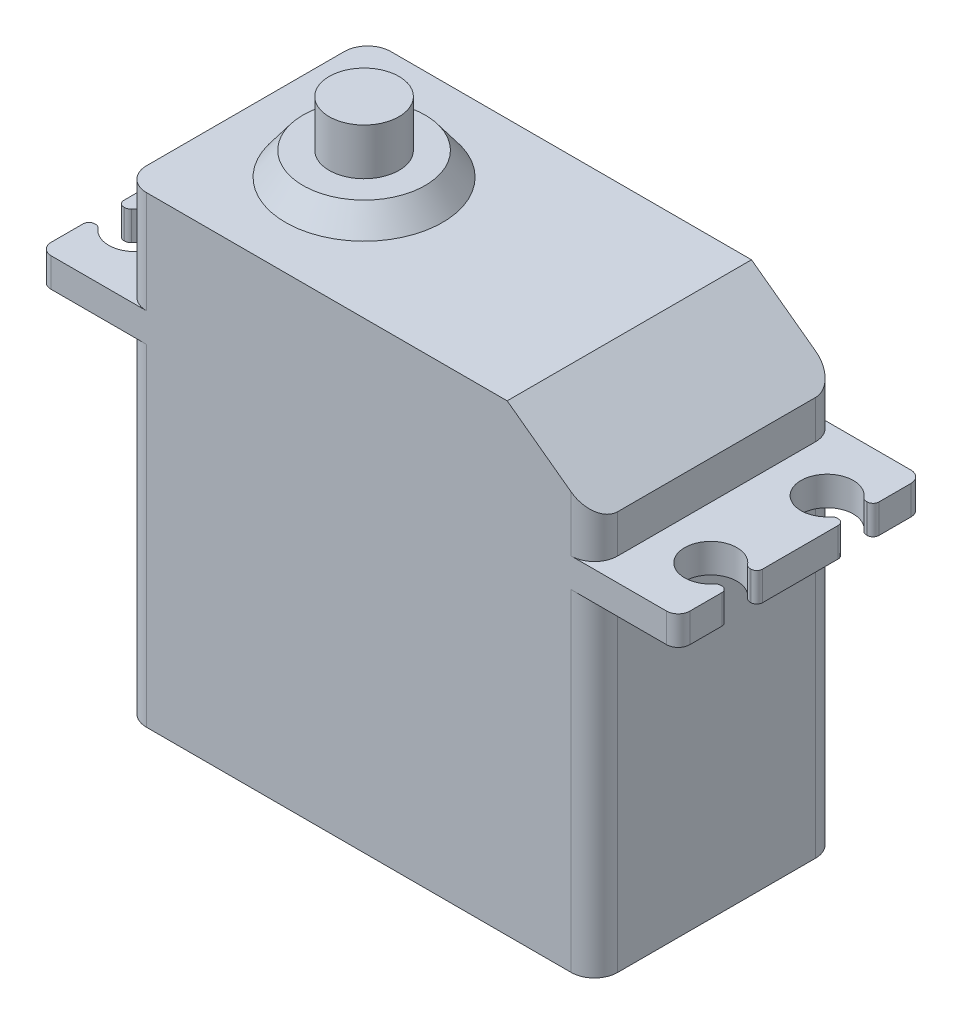
SolidWorks part; units mm, degrees
ref_plane "Plan de face" through (0, 0, 0) normal (0, 0, 1) x (1, 0, 0)
ref_plane "Plan de dessus" through (0, 0, 0) normal (0, 1, 0) x (1, 0, 0)
ref_plane "Plan de droite" through (0, 0, 0) normal (1, 0, 0) x (0, 0, -1)
sketch "Esquisse1" plane through (0, 0, 0) normal (0, 0, 1) x (1, 0, 0)
  line L0 (0, 0) -> (40.5, 0)
  line L1 (40.5, 0) -> (40.5, 34.3)
  line L2 (40.5, 34.3) -> (33, 39.8)
  line L3 (33, 39.8) -> (0, 39.8)
  line L4 (0, 39.8) -> (0, 0)
  dimension "D1" = 39.8
  dimension "D2" = 40.5
  dimension "D3" = 5.5
  dimension "D4" = 7.5
extrude "Extrusion1" add sketch "Esquisse1" against normal blind 21
sketch "Esquisse2" plane through (40.5, 0, 0) normal (1, 0, 0) x (0, 0, -1)
  line L0 (0, 28.5) -> (21, 28.5)
  line L1 (21, 0) -> (21, 34.3) construction
  line L2 (21, 28.5) -> (21, 31)
  line L3 (21, 31) -> (0, 31)
  line L4 (0, 31) -> (0, 28.5)
  line L5 (0, 0) -> (0, 34.3) construction
  line L6 (21, 0) -> (0, 0) construction
  dimension "D1" = 2.5
  dimension "D2" = 28.5
extrude "Extrusion2" add sketch "Esquisse2" along normal blind 7.2
sketch "Esquisse3" plane through (0, 0, 0) normal (-1, 0, 0) x (0, 0, 1)
  line L0 (-21, 31) -> (0, 31)
  line L1 (0, 31) -> (0, 28.5)
  line L2 (0, 28.5) -> (-21, 28.5)
  line L3 (-21, 39.8) -> (-21, 0) construction
  line L4 (0, 28.5) -> (-21, 28.5) construction
  line L5 (-21, 28.5) -> (-21, 31)
extrude "Extrusion3" add sketch "Esquisse3" along normal blind 7.2
sketch "Esquisse4" plane through (0, 31, 0) normal (0, 1, 0) x (-1, 0, 0)
  line L0 (-20.25, -21) -> (-20.25, 0) construction
  line L1 (-33, -21) -> (0, -21) construction
  line L2 (-33, 0) -> (0, 0) construction
  line L3 (7.2, -10.5) -> (-47.7, -10.5) construction
  line L4 (7.2, 0) -> (7.2, -21) construction
  line L5 (-47.7, -21) -> (-47.7, 0) construction
  circle A0 centre (4.5, -15.5) radius 2.25
  circle A1 centre (-45, -15.5) radius 2.25
  circle A2 centre (-45, -5.5) radius 2.25
  circle A3 centre (4.5, -5.5) radius 2.25
  point P2 (-20.25, -10.5)
  dimension "D1" = 4.5
  dimension "D2" = 5
  dimension "D3" = 24.75
extrude "Extrusion4" cut sketch "Esquisse4" against normal up to next
fillet "Congé1" radius 1 4 edges at (47.7, 29.75, 0) (47.7, 29.75, -21) (-7.2, 29.75, -21) (-7.2, 29.75, 0)
fillet "Congé2" radius 2 8 edges
sketch "Esquisse5" plane through (0, 39.8, 0) normal (0, 1, 0) x (-1, 0, 0)
  line L0 (0, -10.5) -> (-33, -10.5) construction
  line L1 (0, -2) -> (0, -19) construction
  line L2 (-33, -21) -> (-33, 0) construction
  circle A0 centre (-10.2, -10.5) radius 3
  dimension "D1" = 6
  dimension "D2" = 10.2
extrude "Extrusion5" add sketch "Esquisse5" along normal blind 6
sketch "Esquisse7" plane through (0, 39.8, 0) normal (0, 1, 0) x (-1, 0, 0)
  circle A0 centre (-10.2, -10.5) radius 6.75
  point P0 (-10.2, -10.5)
  dimension "D1" = 13.5
extrude "Extrusion6" add sketch "Esquisse7" along normal blind 2
chamfer "Chanfrein1" distance 2 distance2 1.5 1 edges at (3.45, 41.8, -10.5) first distance on face at (3.45, 41.8, -10.5)
sketch "Esquisse8" plane through (0, 31, 0) normal (0, 1, 0) x (-1, 0, 0)
  line L0 (7.2, -16.75) -> (6.2, -16.75)
  line L1 (7.2, -1) -> (7.2, -20) construction
  line L2 (6.2, -16.75) -> (6.2, -14.25)
  line L3 (6.2, -14.25) -> (7.2, -14.25)
  line L4 (7.2, -14.25) -> (7.2, -16.75)
  line L5 (-47.7, -10.5) -> (7.2, -10.5) construction
  line L6 (-47.7, -20) -> (-47.7, -1) construction
  line L7 (-20.25, -21) -> (-20.25, 0) construction
  line L8 (-33, -21) -> (-2, -21) construction
  line L9 (-33, 0) -> (-2, 0) construction
  line L10 (7.2, -6.75) -> (7.2, -4.25)
  line L11 (7.2, -4.25) -> (6.2, -4.25)
  line L12 (6.2, -4.25) -> (6.2, -6.75)
  line L13 (6.2, -6.75) -> (7.2, -6.75)
  line L14 (-47.7, -14.25) -> (-47.7, -16.75)
  line L15 (-47.7, -16.75) -> (-46.7, -16.75)
  line L16 (-46.7, -16.75) -> (-46.7, -14.25)
  line L17 (-46.7, -14.25) -> (-47.7, -14.25)
  line L18 (-46.7, -6.75) -> (-47.7, -6.75)
  line L19 (-47.7, -6.75) -> (-47.7, -4.25)
  line L20 (-47.7, -4.25) -> (-46.7, -4.25)
  line L21 (-46.7, -4.25) -> (-46.7, -6.75)
  point P16 (-20.25, -10.5)
  point P20 (6.2, -15.5)
  dimension "D1" = 5
  dimension "D2" = 2.5
  dimension "D3" = 1
extrude "Extrusion7" cut sketch "Esquisse8" against normal up to next
fillet "Congé3" radius 0.5 16 edges at (-7.2, 29.75, -16.75) (-6.3708, 29.75, -16.75) (-6.3708, 29.75, -6.75) (-7.2, 29.75, -6.75) (-6.3708, 29.75, -14.25) (-7.2, 29.75, -14.25) (-6.3708, 29.75, -4.25) (-7.2, 29.75, -4.25) (46.8708, 29.75, -16.75) (47.7, 29.75, -16.75) (46.8708, 29.75, -14.25) (47.7, 29.75, -14.25) (47.7, 29.75, -6.75) (46.8708, 29.75, -6.75) (46.8708, 29.75, -4.25) (47.7, 29.75, -4.25)
sketch "Esquisse9" plane through (0, 0, 0) normal (0, -1, 0) x (1, 0, 0)
  circle A0 centre (10.2, -10.5) radius 7
  circle A1 centre (10.2, -10.5) radius 1.5
  point P0 (10.2, -10.5)
  dimension "D1" = 14
  dimension "D2" = 3
extrude "Extrusion8" add sketch "Esquisse9" along normal blind 2.4
fillet "Congé4" radius 0.5 1 edges at (10.2, -2.4, -17.5)
